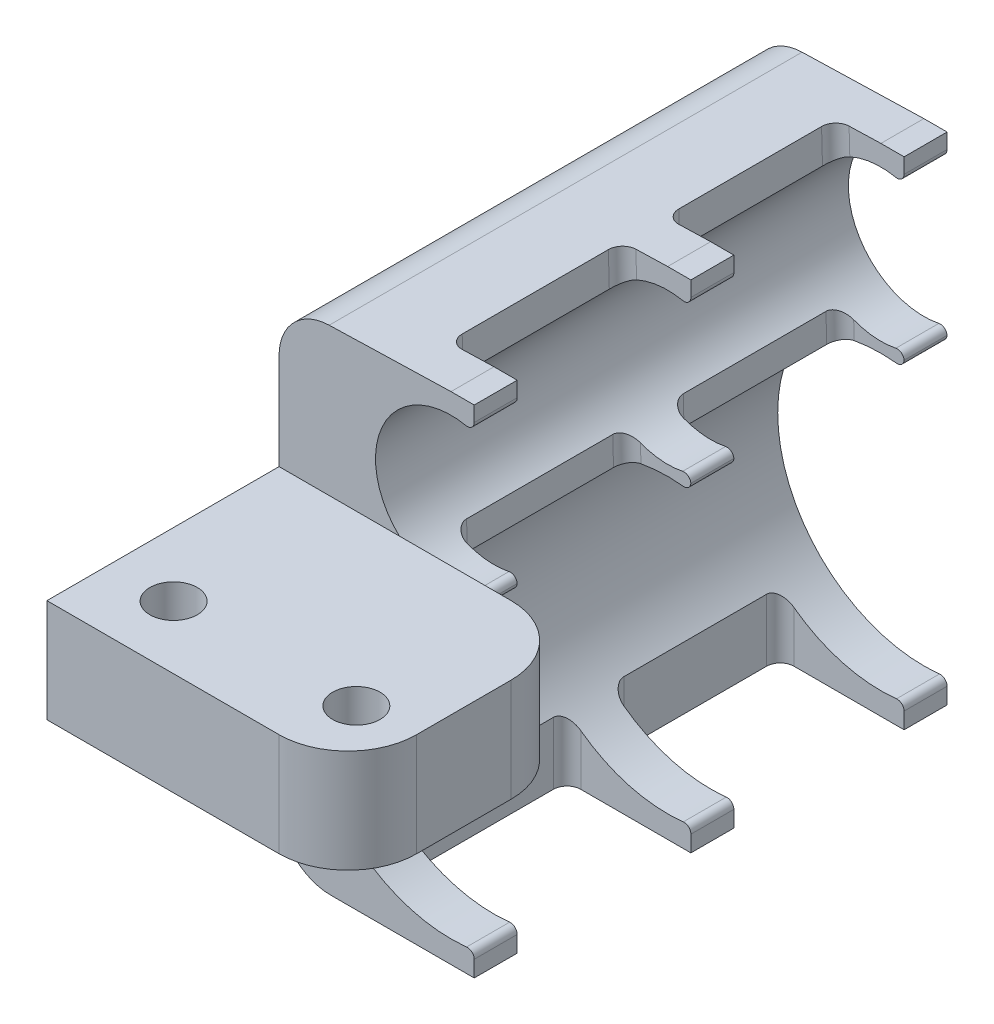
SolidWorks part; units mm, degrees
ref_plane "Front Plane" through (0, 0, 0) normal (0, 0, 1) x (1, 0, 0)
ref_plane "Top Plane" through (0, 0, 0) normal (0, 1, 0) x (1, 0, 0)
ref_plane "Right Plane" through (0, 0, 0) normal (1, 0, 0) x (0, 0, -1)
sketch "Sketch1" plane through (0, 0, 0) normal (0, 0, 1) x (1, 0, 0)
  line L0 (0, 0) -> (0, 13.2295) construction
  line L1 (3.429, -21.316) -> (3.429, -24.872)
  line L2 (0, -24.872) -> (-25.4, -24.872)
  line L3 (-25.4, 47.7241) -> (-25.4, -24.872)
  line L4 (3.429, 23.6544) -> (3.429, 21.316)
  line L5 (0, 48.4296) -> (-25.4, 47.7241)
  line L8 (0, 48.4296) -> (3.429, 48.4296)
  line L9 (3.429, 48.4296) -> (3.429, 44.8736)
  line L10 (3.429, -24.872) -> (0, -24.872)
  circle A0 centre (0, 0) radius 21.59 construction
  arc A1 (3.429, 21.316) -> (3.429, -21.316) centre (0, 0) ccw
  arc A2 (3.429, 44.8736) -> (3.429, 23.6544) centre (0, 34.264) ccw
  dimension "D1" = 22.3
  dimension "D2" = 3.556
  dimension "D3" = 3.556
  dimension "D4" = 3.429
  dimension "D5" = 25.4
extrude "Boss-Extrude1" add sketch "Sketch1" against normal blind 69.85
sketch "Sketch2" plane through (-1.3441, 48.3923, 0) normal (-0.0278, 0.9996, 0) x (0.9996, 0.0278, 0)
  line L0 (4.7723, 69.85) -> (4.7723, 0) construction
  line L1 (-5.3877, 63.5) -> (10.6572, 63.5)
  line L2 (-5.3877, 63.5) -> (-5.3877, 38.3544)
  line L3 (-5.3877, 38.3544) -> (10.6572, 38.3544)
  line L4 (10.6572, 63.5) -> (10.6572, 38.3544)
  line L5 (-5.3877, 32.0044) -> (10.6572, 32.0044)
  line L6 (-5.3877, 32.0044) -> (-5.3877, 6.35)
  line L7 (-5.3877, 6.35) -> (10.6572, 6.35)
  line L8 (10.6572, 32.0044) -> (10.6572, 6.35)
  line L9 (1.3446, 69.85) -> (-24.0652, 69.85) construction
  line L10 (1.3446, 0) -> (-24.0652, 0) construction
  dimension "D1" = 10.16
  dimension "D2" = 10.16
  dimension "D3" = 6.35
  dimension "D4" = 6.35
  dimension "D5" = 6.35
extrude "Cut-Extrude1" cut sketch "Sketch2" against normal through all and the other way blind 2.54
sketch "Sketch3" plane through (0, -24.872, 0) normal (0, -1, 0) x (1, 0, 0)
  line L0 (3.429, -32.0044) -> (-4.6989, -32.0044) construction
  line L1 (-4.6989, -6.35) -> (-14.8589, -6.35)
  line L3 (-7.6834, -32.0044) -> (-14.8589, -32.0044)
  line L4 (-14.8589, -6.35) -> (-14.8589, -32.0044)
  line L5 (-4.6989, -38.3544) -> (-14.8589, -38.3544)
  line L7 (-7.6834, -63.5) -> (-14.8589, -63.5)
  line L8 (-14.8589, -38.3544) -> (-14.8589, -63.5)
  line L9 (-4.6989, -6.35) -> (-4.3793, -6.35)
  line L11 (-7.6834, -32.0044) -> (-4.3793, -32.0044)
  line L12 (-4.3793, -6.35) -> (-4.3793, -32.0044)
  line L13 (3.429, -63.5) -> (-4.6989, -63.5) construction
  line L14 (-4.6989, -38.3544) -> (-2.4227, -38.3544)
  line L16 (-7.6834, -63.5) -> (-2.4227, -63.5)
  line L17 (-2.4227, -38.3544) -> (-2.4227, -63.5)
  dimension "D1" = 10.16
  dimension "D2" = 10.16
extrude "Cut-Extrude2" cut sketch "Sketch3" against normal blind 13.97
fillet "Fillet1" radius 1.016 12 edges at (3.429, 23.6544, -3.175) (3.429, -21.316, -3.175) (3.429, -21.316, -35.1794) (3.429, -21.316, -66.675) (3.429, 23.6544, -35.1794) (3.429, 23.6544, -66.675) (3.429, 44.8736, -3.175) (3.429, 44.8736, -35.1794) (3.429, 44.8736, -66.675) (3.429, 21.316, -66.675) (3.429, 21.316, -35.1794) (3.429, 21.316, -3.175)
fillet "Fillet2" radius 2.032 12 edges at (-6.6605, 45.75, -63.5) (-6.6605, 45.75, -32.0044) (-6.024, 22.834, -32.0044) (-6.024, 22.834, -63.5) (-14.8589, -20.2676, -63.5) (-14.8589, -20.2676, -38.3544) (-14.8589, -20.2676, -6.35) (-6.024, 22.834, -38.3544) (-6.6605, 45.75, -38.3544) (-6.6605, 45.75, -6.35) (-6.024, 22.834, -6.35) (-14.8589, -20.2676, -32.0044)
sketch "Sketch4" plane through (-25.4, 0, 0) normal (-1, 0, 0) x (0, 0, 1)
  line L0 (-69.85, 47.7241) -> (0, 47.7241) construction
  line L5 (0, 23.114) -> (0, 45.414) construction
  line L6 (0, 26.1341) -> (34.29, 26.1341)
  line L7 (0, 26.1341) -> (0, 10.8941)
  line L8 (0, 10.8941) -> (34.29, 10.8941)
  line L9 (34.29, 26.1341) -> (34.29, 10.8941)
  dimension "D1" = 15.24
  dimension "D2" = 21.59
  dimension "D3" = 34.29
extrude "Boss-Extrude2" add sketch "Sketch4" against normal blind 44.45
fillet "Fillet3" radius 10.16 2 edges at (19.05, 18.5141, 34.29) (19.05, 18.5141, 0)
sketch "Sketch5" plane through (0, 26.1341, 0) normal (0, 1, 0) x (1, 0, 0)
  line L0 (-25.4, -34.29) -> (-25.4, 0) construction
  line L1 (8.89, -34.29) -> (-25.4, -34.29) construction
  circle A0 centre (10.91, -24.892) radius 3.5
  circle A1 centre (-15.98, -25) radius 3.5
  point P0 (-15.98, -25)
  point P1 (10.91, -24.892)
  dimension "D5" = 7
  dimension "D1" = 26.89
  dimension "D2" = 9.42
  dimension "D3" = 9.29
  dimension "D4" = 9.398
extrude "Cut-Extrude3" cut sketch "Sketch5" against normal through all
fillet "Fillet4" radius 7.62 2 edges at (-25.4, -24.872, -34.925) (-25.4, 47.7241, -34.925)
